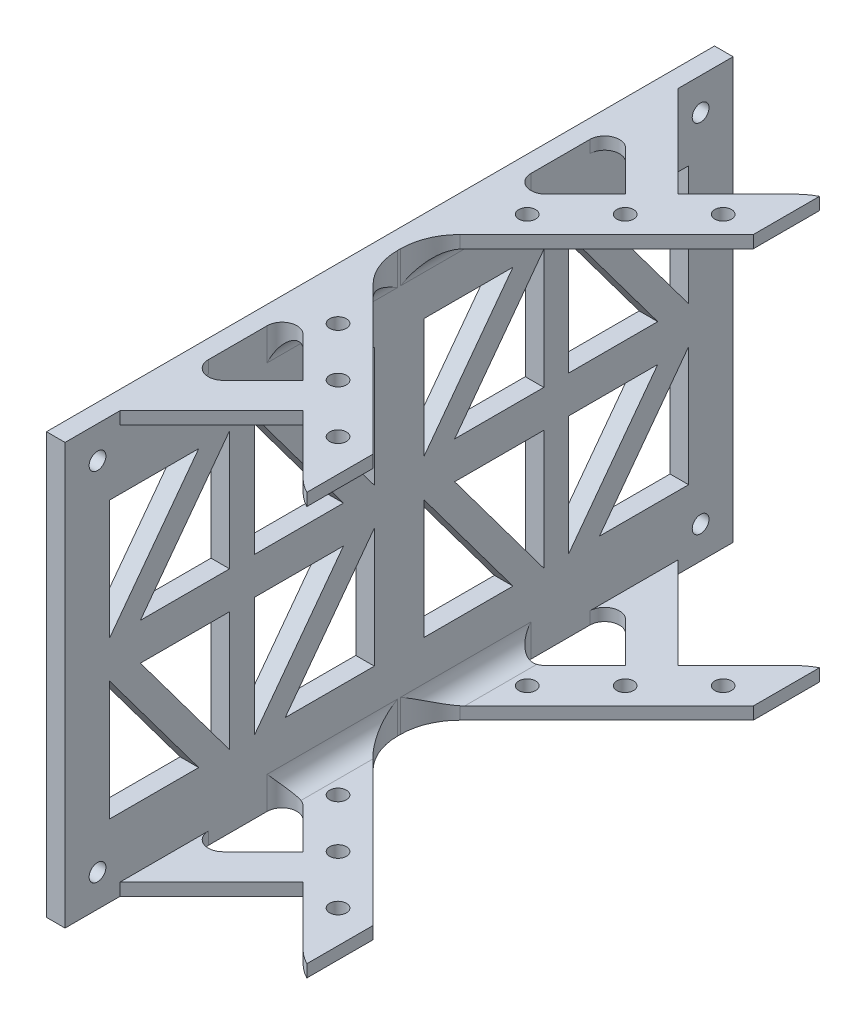
SolidWorks part; units mm, degrees
note: '?' marks a value the reader was unsure of.
material "bat_cradle_mat"
ref_plane "Front Plane" through (0, 0, 0) normal (0, 0, 1) x (1, 0, 0)
ref_plane "Top Plane" through (0, 0, 0) normal (0, 1, 0) x (1, 0, 0)
ref_plane "Right Plane" through (0, 0, 0) normal (1, 0, 0) x (0, 0, -1)
sketch "Sketch1" plane through (0, 0, 0) normal (0, 1, 0) x (1, 0, 0)
  line L4 (0, 0) -> (-125.5226, 0) construction
  line L5 (0, 0) -> (0, -105.5552) construction
  line L6 (-82.6777, 0) -> (0, -82.677)
  line L7 (0, -82.677) -> (0, -64.7166)
  line L8 (0, -64.7166) -> (-64.7172, 0)
  line L9 (-64.7172, 0) -> (-82.6777, 0)
  dimension "D1" = 12.7
  dimension "D2" = 116.9235
extrude "Boss-Extrude2" add sketch "Sketch1" along normal blind 3.175
mirror "Mirror1" about plane through (0, 0, 0) normal (0, 0, 1) of "Boss-Extrude2"
sketch "Sketch6" [suppressed] plane through (0, 3.175, 0) normal (0, 1, 0) x (1, 0, 0)
  circle A0 centre (0, -69.85) radius 7.874
  dimension "D1" = 69.85
hole_wizard "F (0.257) Diameter Hole1" [suppressed] positions "Sketch4" profile "Sketch5" hole size "F" standard "ANSI Inch"
sketch "Sketch4" plane through (0, 3.175, 0) normal (0, 1, 0) x (1, 0, 0)
  circle A0 centre (-69.85, 0) radius 9.525
  point P0 (-69.85, 0)
  point P7 (-69.85, 0)
  point P11 (-69.85, 0)
  point P13 (-69.85, 0)
  dimension "D2" = 19.05
  dimension "D1" = 69.85
sketch "Sketch5" plane through (-69.85, 3.175, 0) normal (1, 0, 0) x (0, 0, 1)
  line L0 (0, 0) -> (0, 52.7611)
  line L1 (0, 52.7611) -> (3.2639, 50.8)
  line L2 (3.2639, 50.8) -> (3.2639, 0)
  line L5 (3.2639, 0) -> (0, 0)
  line L10 (0, 52.7611) -> (-3.2639, 50.8) construction
  line L11 (0, -6.35) -> (0, 107.95) construction
  dimension "Hole Dia." = 6.5278
  dimension "Hole Depth" = 50.8
  dimension "Drill Angle" = 118
ref_axis "Axis1" through (0, 0, 0) along (0, 1, 0)?
sketch "Sketch7" plane through (0, 3.175, 0) normal (0, 1, 0) x (1, 0, 0)
  line L1 (-82.6777, 0) -> (0, -82.677) construction
  line L2 (-36.8488, -36.8484) -> (-41.3389, -41.3385) construction
  line L4 (-49.4211, -24.276) -> (-24.2764, -49.4207) construction
  circle A0 centre (-36.8488, -36.8484) radius 2.1527
  circle A1 centre (-49.4211, -24.276) radius 2.1526
  circle A2 centre (-24.2764, -49.4207) radius 2.1527
  point P8 (-36.8488, -36.8484)
  dimension "D1" = 4.3053
  dimension "D4" = 4.3053
  dimension "D5" = 4.3053
  dimension "D2" = 6.35
  dimension "D3" = 35.56
extrude "Cut-Extrude1" cut sketch "Sketch7" against normal through all
mirror "Mirror2" about plane through (0, 0, 0) normal (0, 0, 1) of "Cut-Extrude1"
fillet "Fillet1" radius 15.24 2 edges at (0, 1.5875, 82.677) (0, 1.5875, -82.677)
fillet "Fillet3" radius 5.08 1 edges at (-82.6777, 1.5875, 0)
sketch "Sketch8" plane through (0, 3.175, 0) normal (0, 1, 0) x (1, 0, 0)
  line L1 (-62.7935, 40.7042) -> (-119.4418, 40.7042)
  line L2 (-62.7935, 40.7042) -> (-62.7935, -60.4946)
  line L3 (-62.7935, -60.4946) -> (-119.4418, -60.4946)
  line L4 (-119.4418, 40.7042) -> (-119.4418, -60.4946)
  arc A0 (-79.0856, 3.5921) -> (-79.0856, -3.5921) centre (-75.4935, 0) ccw construction
  dimension "D1" = 12.7
extrude "Cut-Extrude2" cut sketch "Sketch8" against normal blind 7.62
sketch "Sketch9" plane through (0, 3.175, 0) normal (0, 1, 0) x (1, 0, 0)
  line L0 (0, 0) -> (-116.062, 0) construction
  line L6 (-62.7935, 85.725) -> (-58.031, 85.725)
  line L7 (-62.7935, 85.725) -> (-62.7935, -85.725)
  line L8 (-62.7935, -85.725) -> (-58.031, -85.725)
  line L9 (-58.031, 85.725) -> (-58.031, -85.725)
  line L10 (-62.7935, -19.8841) -> (-62.7935, -1.9236) construction
  point P9 (-58.031, 0)
  dimension "D1" = 4.7625
  dimension "D2" = 171.45
extrude "Boss-Extrude3" add sketch "Sketch9" along normal blind 53.975 from offset 3.175 offset against normal yes
sketch "Sketch15" plane through (0, 0, 0) normal (0, -1, 0) x (1, 0, 0)
  line L5 (-41.282, 41.3953) -> (-58.031, 58.1444)
  line L6 (-58.031, 24.6465) -> (-19.6058, 63.0713) construction
  line L7 (-58.031, 85.725) -> (-58.031, 24.6465) construction
  line L8 (-34.5468, 48.1305) -> (-58.031, 71.6149)
  line L9 (-58.031, 71.6149) -> (-58.031, 58.1444)
  line L10 (-34.5468, 48.1305) -> (-41.282, 41.3953)
  dimension "D1" = 9.525
extrude "Boss-Extrude4" add sketch "Sketch15" against normal blind 3.175
mirror "Mirror10" about plane through (0, 0, 0) normal (0, 0, 1) of "Boss-Extrude4"
fillet "Fillet5" radius 15.24 2 edges at (-58.031, 1.5875, 6.6861) (-58.031, 1.5875, -6.6861)
fillet "Fillet6" radius 3.81 4 edges at (-58.031, 1.5875, 24.6465) (-58.031, 1.5875, -24.6465) (-58.031, 1.5875, 58.1444) (-58.031, 1.5875, -58.1444)
fillet "Fillet7" radius 5.08 2 edges at (-58.031, 3.175, 17.109) (-58.031, 3.175, -17.109)
sketch "Sketch11" plane through (0, 3.175, 0) normal (0, 1, 0) x (1, 0, 0)
  line L1 (-15.9146, -90.0073) -> (30.2962, -90.0073)
  line L2 (-15.9146, -90.0073) -> (-15.9146, 90.9112)
  line L3 (-15.9146, 90.9112) -> (30.2962, 90.9112)
  line L4 (30.2962, -90.0073) -> (30.2962, 90.9112)
extrude "Cut-Extrude4" cut sketch "Sketch11" against normal blind 6.35
mirror "Mirror6" about plane through (0, 53.975, 0) normal (0, 1, 0) of bodies 116 112
sketch "Sketch12" plane through (-58.031, 0, 0) normal (1, 0, 0) x (0, 0, -1)
  line L0 (0, 107.95) -> (0, 0) construction
  line L1 (-6.6861, 107.95) -> (6.6861, 107.95) construction
  line L2 (-85.725, 53.975) -> (85.725, 53.975) construction
  line L3 (85.725, 107.95) -> (85.725, 0) construction
  circle A0 centre (-77.3906, 99.695) radius 2.1527
  point P10 (0, 53.975)
  dimension "D1" = 4.3053
  dimension "D3" = 45.72
  dimension "D2" = 77.3906
extrude "Cut-Extrude5" cut sketch "Sketch12" against normal through all contours A0
ref_plane "Plane1" through (0, 53.975, 0) normal (0, -1, 0) x (-1, 0, 0)
mirror "Mirror7" about plane through (0, 0, 0) normal (0, 0, 1) of "Cut-Extrude5" second plane through (0, 53.975, 0) second plane normal (0, -1, 0)
sketch "Sketch14" plane through (-58.031, 0, 0) normal (1, 0, 0) x (0, 0, -1)
  line L0 (-6.35, 49.2125) -> (-6.35, 18.5345)
  line L1 (-6.35, 18.5345) -> (-29.2323, 18.5345)
  line L2 (-29.2323, 18.5345) -> (-6.35, 49.2125)
  line L3 (-37.1542, 18.5345) -> (-37.1542, 49.2125)
  line L4 (-37.1542, 49.2125) -> (-14.2719, 49.2125)
  line L5 (-14.2719, 49.2125) -> (-37.1542, 18.5345)
  line L6 (-29.2323, 18.5345) -> (-37.1542, 18.5345) construction
  line L7 (-41.9167, 13.9139) -> (-41.9167, 52.8346) construction
  line L8 (0, 0) -> (0, 51.4065) construction
  line L10 (-2.6194, 53.975) -> (2.6194, 53.975) construction
  dimension "D1" = 6.35
  dimension "D2" = 4.7625
  dimension "D3" = 6.35
  dimension "D4" = 4.7625
extrude "Cut-Extrude6" cut sketch "Sketch14" against normal through all contours L2 L0 L1 | L3 L4 L5
fillet "Fillet8" [suppressed] radius 2.54
ref_plane "Plane2" through (0, 0, 40.3292) normal (0, 0, -1) x (-1, 0, 0)
mirror "Mirror8" about plane through (0, 0, 40.3292) normal (0, 0, -1) of "Cut-Extrude6"
mirror "Mirror9" about plane through (0, 53.975, 0) normal (0, -1, 0) of "Mirror8", "Cut-Extrude6" second plane through (0, 0, 0) second plane normal (0, 0, 1)
